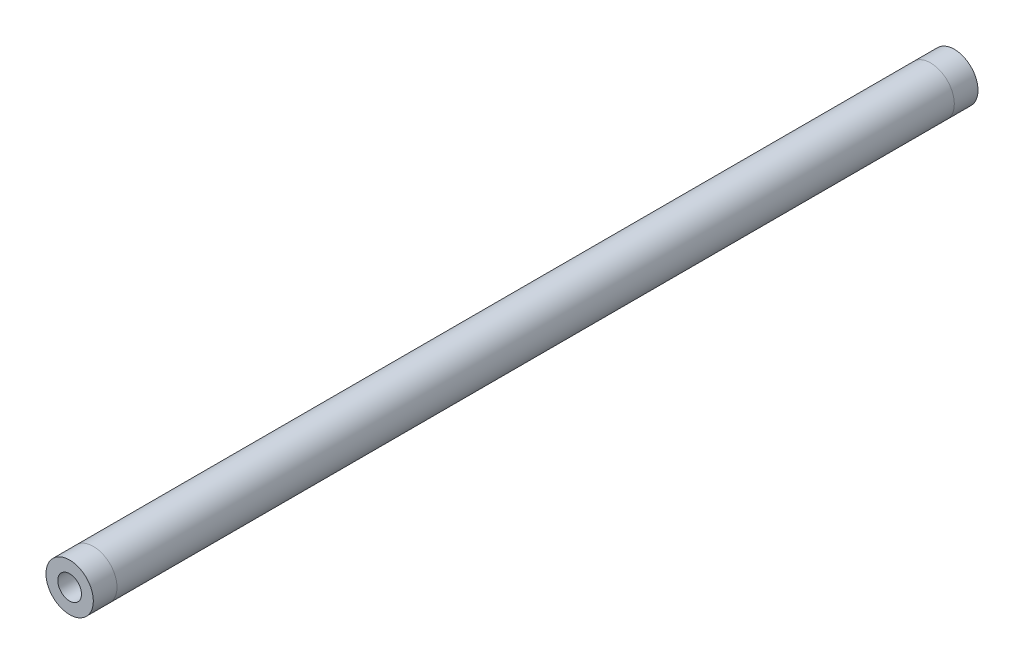
SolidWorks part; units mm, degrees
material "AISI 4130 Steel, normalized at 870C"
ref_plane "Front Plane" through (0, 0, 0) normal (0, 0, 1) x (1, 0, 0)
ref_plane "Top Plane" through (0, 0, 0) normal (0, 1, 0) x (1, 0, 0)
ref_plane "Right Plane" through (0, 0, 0) normal (1, 0, 0) x (0, 0, -1)
sketch "Axis" plane through (0, 0, 0) normal (1, 0, 0) x (0, 0, -1)
  line L0 (0, 0) -> (237.2056, 0) construction
  line L1 (237.2056, 0) -> (230.8556, 0)
  line L2 (237.2056, 0) -> (259.1004, 0) construction
  line L3 (0, 0) -> (-21.8948, 0) construction
  point P4 (0, 0)
  point P5 (237.2056, 0)
  point P6 (230.8556, 0)
  dimension "D1" = 6.35
  dimension "D2" = 21.8948
  dimension "D3" = 21.8948
sketch "Sketch1" plane through (0, 0, 0) normal (0, 0, 1) x (1, 0, 0)
  circle A0 centre (0, 0) radius 6.35
  circle A1 centre (0, 0) radius 4.8768
  circle A2 centre (0, 0) radius 3.175
  dimension "D1" = 12.7
  dimension "D2" = 1.4732
  dimension "D3" = 6.35
extrude "Threaded insert 1-1" add sketch "Sketch1" against normal blind 6.35 contours A0 A1 | A1 A2 region at (-6.1704, 0, 0) region at (-4.7389, 0, 0)
extrude "Threaded insert 1-2" add sketch "Sketch1<3>" against normal blind 9.525 from surface contours A1 A2 region at (-4.7389, 0, 0) starting at face at (6.35, 0, -6.35)
sketch "Sketch1<3>" plane through (0, 0, 0) normal (0, 0, 1) x (1, 0, 0) same geometry as "Sketch1"
extrude "Tube extrude" add sketch "Sketch1<4>" against normal up to vertex (230.8556 mm away) from surface separate body contours A0 A1 region at (-6.1704, 0, 0) up to point (0, 0, -230.8556) starting at face at (4.8768, 0, -6.35)
sketch "Sketch1<4>" plane through (0, 0, 0) normal (0, 0, 1) x (1, 0, 0) same geometry as "Sketch1"
extrude "Threaded insert 2-1" add sketch "Sketch1<6>" along normal blind 9.525 from surface separate body contours A1 A2 region at (-4.7389, 0, 0) starting at face at (4.8768, 0, -230.8556)
sketch "Sketch1<6>" plane through (0, 0, 0) normal (0, 0, 1) x (1, 0, 0) same geometry as "Sketch1"
extrude "Threaded insert 2-2" add sketch "Sketch1<9>" against normal blind 6.35 from surface separate body contours A1 A2 | A0 A1 region at (-6.1704, 0, 0) region at (-4.7389, 0, 0) starting at face at (4.8768, 0, -230.8556)
sketch "Sketch1<9>" plane through (0, 0, 0) normal (0, 0, 1) x (1, 0, 0) same geometry as "Sketch1"
combine bodies "Combine1" operation type add bodies to combine 106 104
equation "\"Threaded insert outer thickness\"= .25"
equation "\"D1@Threaded insert 1-1\"=\"Threaded insert outer thickness\""
equation "\"D1@Threaded insert 2-2\"=\"Threaded insert outer thickness\""
equation "\"D1@Axis\" = \"Threaded insert outer thickness\""
